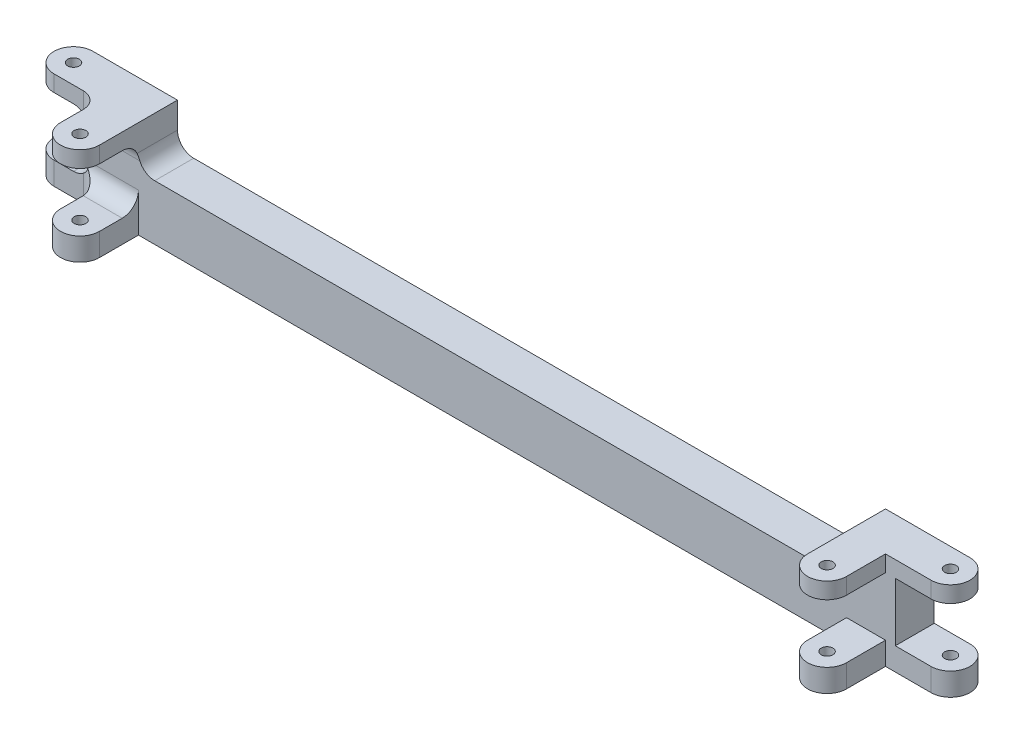
SolidWorks part; units mm, degrees
ref_plane "Front Plane" through (0, 0, 0) normal (0, 0, 1) x (1, 0, 0)
ref_plane "Top Plane" through (0, 0, 0) normal (0, 1, 0) x (1, 0, 0)
ref_plane "Right Plane" through (0, 0, 0) normal (1, 0, 0) x (0, 0, -1)
sketch "Sketch2" plane through (0, 0, 0) normal (0, 1, 0) x (1, 0, 0)
  line L0 (0, 0) -> (-171.45, 0) construction
  line L1 (-146.05, 0) -> (-146.05, -22.86) construction
  line L2 (0, -10.8602) -> (0, 10.8602) construction
  line L3 (0, 7.62) -> (-171.45, 7.62)
  line L4 (-153.67, -7.62) -> (-153.67, -22.86)
  line L5 (138.43, -7.62) -> (-138.43, -7.62)
  line L6 (-138.43, -7.62) -> (-138.43, -22.86)
  line L7 (-153.67, 0) -> (-153.67, -22.86) construction
  line L8 (-153.67, -7.62) -> (-171.45, -7.62)
  line L9 (0, -7.62) -> (-171.45, -7.62) construction
  line L10 (-138.43, 0) -> (-138.43, -22.86) construction
  line L11 (146.05, 0) -> (146.05, -22.86) construction
  line L12 (0, 0) -> (171.45, 0) construction
  line L13 (153.67, -7.62) -> (171.45, -7.62)
  line L14 (138.43, -7.62) -> (138.43, -22.86)
  line L15 (153.67, -7.62) -> (153.67, -22.86)
  line L16 (0, 7.62) -> (171.45, 7.62)
  circle A0 centre (-171.45, 0) radius 2.286
  circle A1 centre (-146.05, -22.86) radius 2.286
  arc A3 (-171.45, 7.62) -> (-171.45, -7.62) centre (-171.45, 0) ccw
  arc A5 (-153.67, -22.86) -> (-138.43, -22.86) centre (-146.05, -22.86) ccw
  arc A6 (153.67, -22.86) -> (138.43, -22.86) centre (146.05, -22.86) cw
  arc A7 (171.45, 7.62) -> (171.45, -7.62) centre (171.45, 0) cw
  circle A8 centre (146.05, -22.86) radius 2.286
  circle A9 centre (171.45, 0) radius 2.286
  point P7 (0, -10.8602)
  point P10 (0, 0)
  point P11 (-116.7558, -12.7)
  dimension "D3" = 4.572
  dimension "D4" = 22.86
  dimension "D5" = 171.45
  dimension "D6" = 25.4
  dimension "D1" = 7.62
  dimension "D2" = 7.62
extrude "Boss-Extrude1" add sketch "Sketch2" along normal blind 8.89
sketch "Sketch3" plane through (0, 8.89, 0) normal (0, 1, 0) x (1, 0, 0)
  line L0 (-171.45, -7.62) -> (-153.67, -7.62) construction
  line L1 (-157.48, -7.62) -> (-138.43, -7.62)
  line L2 (-157.48, -7.62) -> (-157.48, 7.62)
  line L3 (-157.48, 7.62) -> (-138.43, 7.62)
  line L4 (-138.43, -7.62) -> (-138.43, 7.62)
  line L5 (171.45, 7.62) -> (-171.45, 7.62) construction
  point P8 (-138.43, -7.62)
  dimension "D2" = 19.05
extrude "Boss-Extrude2" add sketch "Sketch3" along normal blind 22.86
sketch "Sketch4" plane through (0, 31.75, 0) normal (0, 1, 0) x (1, 0, 0)
  line L69 (-138.43, 7.62) -> (-138.43, -22.86)
  line L87 (-138.43, 7.62) -> (-171.45, 7.62)
  line L88 (-171.45, -7.62) -> (-153.67, -7.62)
  line L89 (-157.48, -7.62) -> (-138.43, -7.62) construction
  line L90 (-153.67, -7.62) -> (-153.67, -22.86) construction
  line L91 (-153.67, -7.62) -> (-153.67, -22.86)
  arc A29 (-153.67, -22.86) -> (-138.43, -22.86) centre (-146.05, -22.86) ccw
  circle A35 centre (-171.45, 0) radius 2.286
  circle A36 centre (-146.05, -22.86) radius 2.286
  circle A37 centre (-171.45, 0) radius 2.286 construction
  arc A44 (-171.45, 7.62) -> (-171.45, -7.62) centre (-171.45, 0) ccw
extrude "Boss-Extrude3" add sketch "Sketch4" along normal blind 6.35
mirror "Mirror1" about plane through (0, 0, 0) normal (1, 0, 0) of "Boss-Extrude3", "Boss-Extrude2"
sketch "Sketch6" plane through (0, 8.89, 0) normal (0, 1, 0) x (1, 0, 0)
  line L1 (-138.43, 7.62) -> (138.43, 7.62)
  line L2 (-138.43, 7.62) -> (-138.43, -7.62)
  line L3 (-138.43, -7.62) -> (138.43, -7.62)
  line L4 (138.43, 7.62) -> (138.43, -7.62)
extrude "Boss-Extrude4" add sketch "Sketch6" along normal blind 12.7
fillet "Fillet4" radius 6.35 3 edges at (-138.43, 21.59, 0) (-157.48, 31.75, 0) (-157.48, 8.89, 0)
fillet "Fillet5" radius 6.35 4 edges at (-153.67, 34.925, 7.62) (-153.67, 4.445, 7.62) (-146.05, 8.89, 7.62) (-146.05, 31.75, 7.62)
